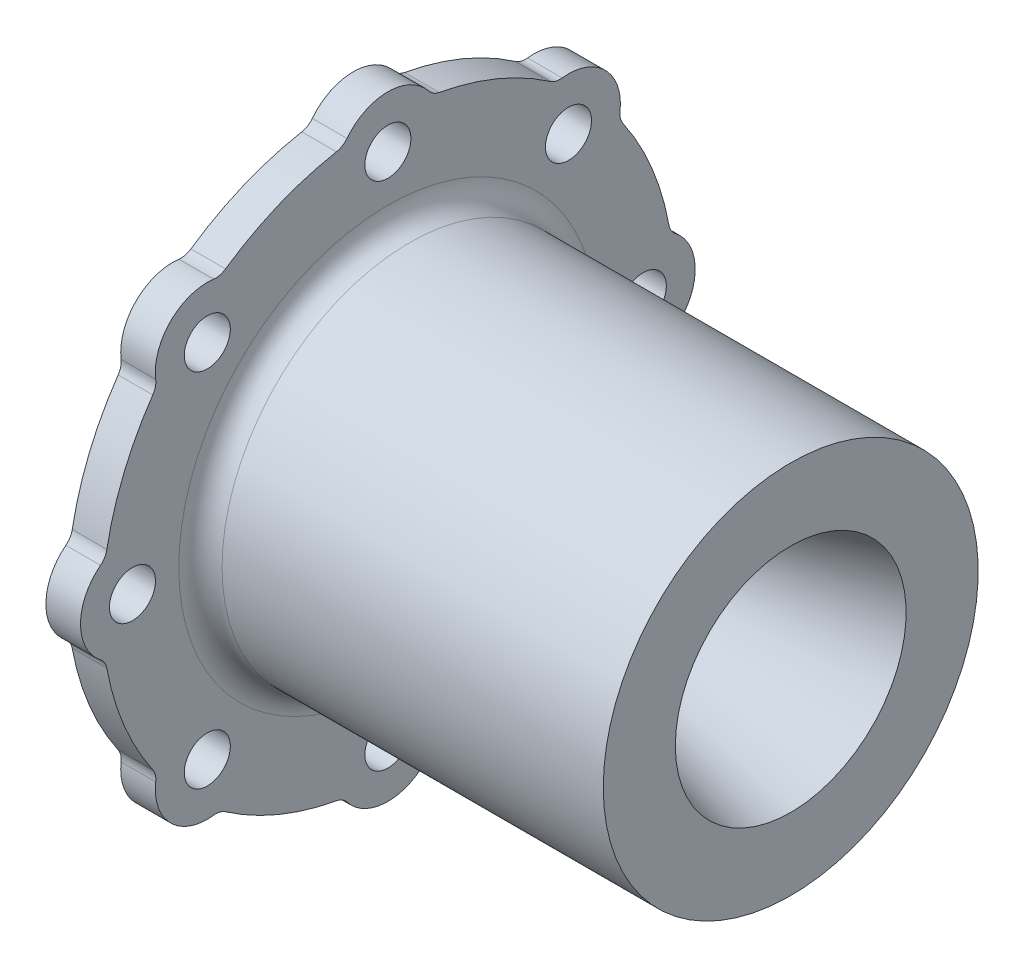
SolidWorks part; units mm, degrees
ref_plane "Front Plane" through (0, 0, 0) normal (0, 0, 1) x (1, 0, 0)
ref_plane "Top Plane" through (0, 0, 0) normal (0, 1, 0) x (1, 0, 0)
ref_plane "Right Plane" through (0, 0, 0) normal (1, 0, 0) x (0, 0, -1)
sketch "Sketch1" plane through (0, 0, 0) normal (0, 0, 1) x (1, 0, 0)
  line L20 (0, 0) -> (32.997, 0) construction
  line L33 (15.4847, 6.946) -> (26.9147, 6.946)
  line L34 (15.4847, 6.946) -> (0, 25.4)
  line L37 (0, 25.4) -> (0, 66.87)
  line L38 (0, 66.87) -> (5.08, 66.87)
  line L39 (5.08, 66.87) -> (5.08, 27.5)
  line L43 (64.1755, 27.5) -> (64.1755, 16.93)
  line L52 (64.1755, 16.93) -> (26.9147, 6.946)
  line L53 (64.1755, 27.5) -> (5.08, 27.5)
  point P1 (2.54, 66.87)
  point P12 (15.4847, 6.946)
  point P24 (26.9147, 6.946)
  dimension "D1" = 6.946
  dimension "D2" = 25.4
  dimension "D5" = 5.08
  dimension "D10" = 15
  dimension "D8" = 16.93
  dimension "D3" = 27.5
  dimension "D4" = 66.87
  dimension "D6" = 11.43
  dimension "D7" = 50
revolve "Nozzle" add sketch "Sketch1" angle 360 about L20
fillet "Rao outlet radius" radius 5.3067 1 edges at (26.9147, 0, 6.946)
sketch "Sketch2" plane through (0, 0, 0) normal (-1, 0, 0) x (0, 0, 1)
  point P0 (37.465, 0)
  point P1 (26.4918, -26.4918)
  point P5 (0, -37.465)
  point P6 (-26.4918, -26.4918)
  point P7 (-37.465, 0)
  point P8 (-26.4918, 26.4918)
  point P9 (0, 37.465)
  point P10 (26.4918, 26.4918)
  point P11 (0, 0)
  dimension "D1" = 37.465
hole_wizard "1/4 Clearance Hole1" positions "Sketch2" profile "Sketch3" hole size "1/4" standard "ANSI Inch" end condition through all
sketch "Sketch3" plane through (0, 0, 37.465) normal (0, 1, 0) x (0, 0, 1)
  line L0 (0, 0) -> (0, 64.1755)
  line L1 (0, 64.1755) -> (3.3782, 64.1755)
  line L2 (3.3782, 64.1755) -> (3.3782, 0)
  line L5 (3.3782, 0) -> (0, 0)
  line L11 (0, -6.35) -> (0, 107.95) construction
  dimension "Thru Hole Dia." = 6.7564
  dimension "Thru Hole Depth" = 64.1755
sketch "Sketch5" plane through (0, 0, 0) normal (1, 0, 0) x (0, 0, -1)
  line L0 (0, 0) -> (0, 85.5504) construction
  arc A32 (6.0027, 42.1589) -> (-6.0027, 42.1589) centre (0, 37.465) ccw
  arc A33 (17.8531, 37.9172) -> (7.5462, 41.225) centre (0, 0) ccw
  arc A51 (-7.5462, 41.225) -> (-14.1874, 39.4356) centre (0, 0) ccw
  arc A69 (6.0027, 42.1589) -> (7.5462, 41.225) centre (8.0035, 43.7235) ccw
  arc A70 (-6.0027, 42.1589) -> (-7.5462, 41.225) centre (-8.0035, 43.7235) cw
  arc A72 (34.0554, 25.5663) -> (25.5663, 34.0554) centre (26.4918, 26.4918) ccw
  arc A73 (39.4356, 14.1874) -> (34.4865, 23.8145) centre (0, 0) ccw
  arc A74 (23.8145, 34.4865) -> (17.8531, 37.9172) centre (0, 0) ccw
  arc A75 (34.0554, 25.5663) -> (34.4865, 23.8145) centre (36.5765, 25.2578) ccw
  arc A76 (25.5663, 34.0554) -> (23.8145, 34.4865) centre (25.2578, 36.5765) cw
  arc A77 (42.1589, -6.0027) -> (42.1589, 6.0027) centre (37.465, 0) ccw
  arc A78 (37.9172, -17.8531) -> (41.225, -7.5462) centre (0, 0) ccw
  arc A79 (41.225, 7.5462) -> (39.4356, 14.1874) centre (0, 0) ccw
  arc A80 (42.1589, -6.0027) -> (41.225, -7.5462) centre (43.7235, -8.0035) ccw
  arc A81 (42.1589, 6.0027) -> (41.225, 7.5462) centre (43.7235, 8.0035) cw
  arc A82 (25.5663, -34.0554) -> (34.0554, -25.5663) centre (26.4918, -26.4918) ccw
  arc A83 (14.1874, -39.4356) -> (23.8145, -34.4865) centre (0, 0) ccw
  arc A84 (34.4865, -23.8145) -> (37.9172, -17.8531) centre (0, 0) ccw
  arc A85 (25.5663, -34.0554) -> (23.8145, -34.4865) centre (25.2578, -36.5765) ccw
  arc A86 (34.0554, -25.5663) -> (34.4865, -23.8145) centre (36.5765, -25.2578) cw
  arc A87 (-6.0027, -42.1589) -> (6.0027, -42.1589) centre (0, -37.465) ccw
  arc A88 (-14.2148, -39.4257) -> (-7.5462, -41.225) centre (0, 0) ccw
  arc A89 (7.5462, -41.225) -> (14.1874, -39.4356) centre (0, 0) ccw
  arc A90 (-6.0027, -42.1589) -> (-7.5462, -41.225) centre (-8.0035, -43.7235) ccw
  arc A91 (6.0027, -42.1589) -> (7.5462, -41.225) centre (8.0035, -43.7235) cw
  arc A92 (-34.0554, -25.5663) -> (-25.5663, -34.0554) centre (-26.4918, -26.4918) ccw
  arc A93 (-37.9194, -17.8486) -> (-34.4865, -23.8145) centre (0, 0) ccw
  arc A94 (-23.8145, -34.4865) -> (-14.2148, -39.4257) centre (0, 0) ccw
  arc A95 (-34.0554, -25.5663) -> (-34.4865, -23.8145) centre (-36.5765, -25.2578) ccw
  arc A96 (-25.5663, -34.0554) -> (-23.8145, -34.4865) centre (-25.2578, -36.5765) cw
  arc A97 (-42.1589, 6.0027) -> (-42.1589, -6.0027) centre (-37.465, 0) ccw
  arc A98 (-39.4483, 14.1519) -> (-41.225, 7.5462) centre (0, 0) ccw
  arc A99 (-41.225, -7.5462) -> (-37.9194, -17.8486) centre (0, 0) ccw
  arc A100 (-42.1589, 6.0027) -> (-41.225, 7.5462) centre (-43.7235, 8.0035) ccw
  arc A101 (-42.1589, -6.0027) -> (-41.225, -7.5462) centre (-43.7235, -8.0035) cw
  arc A102 (-25.5663, 34.0554) -> (-34.0554, 25.5663) centre (-26.4918, 26.4918) ccw
  arc A103 (-14.1874, 39.4356) -> (-23.8145, 34.4865) centre (0, 0) ccw
  arc A104 (-34.4865, 23.8145) -> (-39.4483, 14.1519) centre (0, 0) ccw
  arc A105 (-25.5663, 34.0554) -> (-23.8145, 34.4865) centre (-25.2578, 36.5765) ccw
  arc A106 (-34.0554, 25.5663) -> (-34.4865, 23.8145) centre (-36.5765, 25.2578) cw
  point P69 (0, 0)
  point P78 (-6.5261, 41.3988)
  dimension "D3" = 41.91
  dimension "D4" = 2.54
  dimension "D5" = 37.465
  dimension "D6" = 37.465
  dimension "D1" = 8
extrude "Cut-Extrude1" cut sketch "Sketch5" along normal up to surface (5.08 mm away) flip side to cut up to face at (5.08, 0, 40.8432)
fillet "Fillet1" radius 3.175 1 edges at (5.08, 0, 27.5)
fillet "Rao Inlet radius" radius 20.838 1 edges at (15.4847, 0, 6.946)
equation "\"radius\"= 1in"
equation "\"Flange\"= 0.55in"
equation "\"Length\"= 2cm"
equation "\"Flange_Thickness\"= 0.2in"
equation "\"offset\"= 0.625cm"
equation "\"D2@Sketch1\"=\"radius\""
equation "\"throat\"= 0.6946cm"
equation "\"hole_dia\"= 0.66cm"
equation "\"D1@Sketch1\"=\"throat\""
equation "\"D5@Sketch1\"=\"Flange_Thickness\""
equation "\"Seal_dia\"= 2.5cm"
equation "\"Seal_depth\"= 0.1cm"
equation "\"Seal_width\"= 0.15cm"
equation "\"Nozzle_angle\"= 15"
equation "\"D10@Sketch1\"=\"Nozzle_angle\""
equation "\"nozzle_length\"= 6.34"
equation "\"bolt_head_dia\"=2.3795"
equation "\"bolt_rad\"= \"radius\" + 0.5 * \"Flange\" + 0.2in"
equation "\"scallop_inner_dia\"= 3.3in"
equation "\"exit_rad\"= 1.693cm"
equation "\"D8@Sketch1\"=\"exit_rad\""
equation "\"outside_dia\"= 2.75cm"
equation "\"D3@Sketch1\"=\"outside_dia\""
equation "\"D4@Sketch1\"=\"outside_dia\"+\"Flange\"+\"Buffer\""
equation "\"Scallop_OD\"= 0.6in"
equation "\"D3\"= \"Scallop_OD\" / 2"
equation "\"D4\"= \"scallop_inner_dia\" / 2"
equation "\"D2@Sketch5\"=\"Scallop_OD\"/2"
equation "\"D3@Sketch5\"=\"scallop_inner_dia\"/2"
equation "\"D6@Sketch5\"=\"bolt_rad\""
equation "\"D1@Sketch2\"=\"bolt_rad\""
equation "\"Buffer\"= 1in"
equation "\"D1@Rao Inlet radius\"=3*\"throat\""
equation "\"D1@Rao outlet radius\"=2 * 0.382 * \"throat\""
